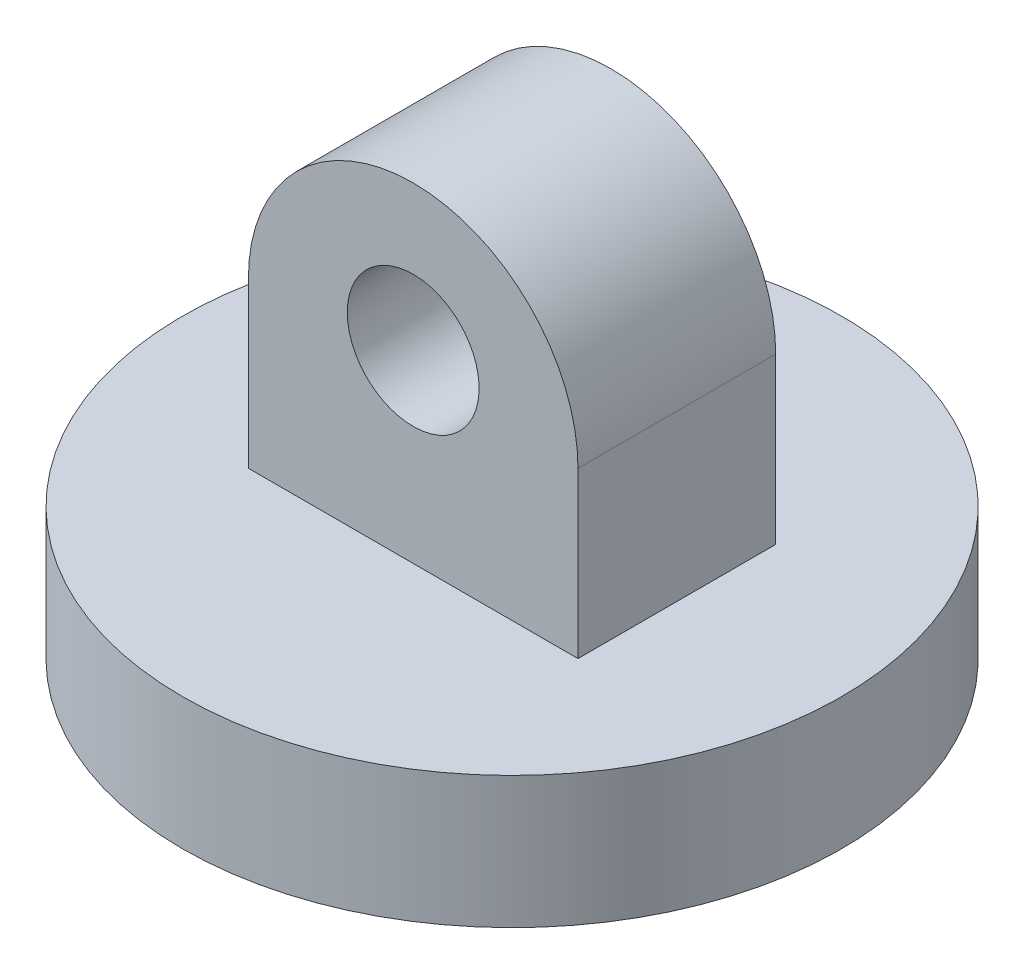
SolidWorks part; units mm, degrees
ref_plane "Alzado" through (0, 0, 0) normal (0, 0, 1) x (1, 0, 0)
ref_plane "Planta" through (0, 0, 0) normal (0, 1, 0) x (1, 0, 0)
ref_plane "Vista lateral" through (0, 0, 0) normal (1, 0, 0) x (0, 0, -1)
sketch "Croquis1" plane through (0, 0, 0) normal (0, 1, 0) x (1, 0, 0)
  circle A0 centre (0, 0) radius 50
  dimension "D1" = 100
extrude "Saliente-Extruir1" add sketch "Croquis1" along normal blind 20
sketch "Croquis2" plane through (0, 20, 0) normal (0, 1, 0) x (1, 0, 0)
  line L0 (-50, 0) -> (50, 0) construction
  line L1 (0, 50) -> (0, -50) construction
  line L3 (-25, 15) -> (25, 15)
  line L4 (-25, 15) -> (-25, -15)
  line L5 (-25, -15) -> (25, -15)
  line L6 (25, 15) -> (25, -15)
  circle A0 centre (0, 0) radius 50 construction
  dimension "D1" = 30
  dimension "D2" = 15
  dimension "D3" = 50
  dimension "D4" = 25
extrude "Saliente-Extruir2" add sketch "Croquis2" along normal blind 50
sketch "Croquis3" plane through (0, 0, -15) normal (0, 0, -1) x (-1, 0, 0)
  line L0 (-25, 70) -> (25, 70) construction
  line L2 (-25, 70) -> (-25, 20) construction
  circle A0 centre (0, 48) radius 10
  dimension "D1" = 20
  dimension "D2" = 22
  dimension "D3" = 25
extrude "Cortar-Extruir1" cut sketch "Croquis3" against normal blind 30
fillet "Redondeo1" 2 edges at (-25, 70, 0) (25, 70, 0) type full round first side face at (-25, 45, 0) second side face at (25, 45, 0) middle face at (0, 70, 0)
